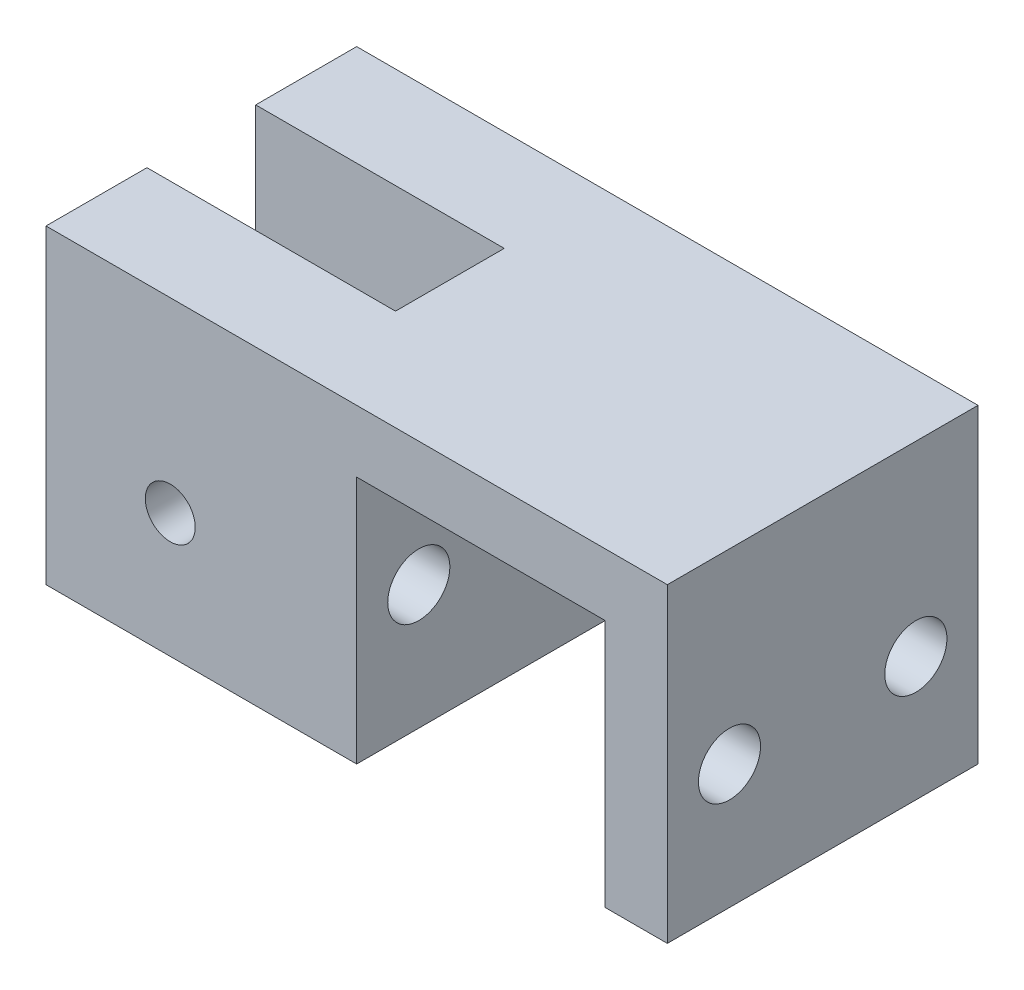
SolidWorks part; units mm, degrees
material "Delrin 2700 NC010, Low Viscosity Acetal Copolymer (SS)"
ref_plane "Front" through (0, 0, 0) normal (0, 0, 1) x (1, 0, 0)
ref_plane "Top" through (0, 0, 0) normal (0, 1, 0) x (1, 0, 0)
ref_plane "Right" through (0, 0, 0) normal (1, 0, 0) x (0, 0, -1)
sketch "Sketch1" plane through (0, 0, 0) normal (0, 0, 1) x (1, 0, 0)
  line L0 (0, 0) -> (0, 25.4)
  line L1 (0, 25.4) -> (25.4, 25.4)
  line L2 (25.4, 25.4) -> (25.4, 0)
  line L3 (25.4, 0) -> (31.75, 0)
  line L4 (31.75, 0) -> (31.75, 31.75)
  line L5 (31.75, 31.75) -> (-31.75, 31.75)
  line L6 (-31.75, 31.75) -> (-31.75, 0)
  line L7 (-31.75, 0) -> (0, 0)
  dimension "D1" = 6.35
  dimension "D2" = 25.4
  dimension "D3" = 6.35
  dimension "D4" = 31.75
extrude "Boss-Extrude1" add sketch "Sketch1" along normal mid plane 31.75
sketch "Sketch2" plane through (0, 31.75, 0) normal (0, 1, 0) x (1, 0, 0)
  line L0 (-31.75, -15.875) -> (-31.75, 15.875) construction
  line L1 (-31.75, 5.5562) -> (-6.35, 5.5562)
  line L2 (-31.75, 5.5562) -> (-31.75, -5.5563)
  line L3 (-31.75, -5.5563) -> (-6.35, -5.5563)
  line L4 (-6.35, 5.5562) -> (-6.35, -5.5563)
  line L5 (-31.75, 15.875) -> (-6.35, 5.5562) construction
  line L6 (-6.35, -5.5563) -> (-31.75, -15.875) construction
  dimension "D1" = 11.1125
  dimension "D2" = 25.4
extrude "Cut-Extrude1" cut sketch "Sketch2" against normal through all
sketch "Sketch5" plane through (31.75, 0, 0) normal (1, 0, 0) x (0, 0, -1)
  line L0 (-15.875, 0) -> (-9.525, 12.7) construction
  line L5 (9.525, 12.7) -> (15.875, 0) construction
  line L7 (-15.875, 0) -> (15.875, 0) construction
  point P0 (-9.525, 12.7)
  point P2 (9.525, 12.7)
  dimension "D1" = 19.05
  dimension "D2" = 12.7
hole_wizard "1/4 (0.25) Diameter Hole1" positions "Sketch5" profile "Sketch4" hole size "1/4" standard "ANSI Inch"
sketch "Sketch4" plane through (31.75, 12.7, 9.525) normal (0, 1, 0) x (0, 0, -1)
  line L0 (0, 0) -> (0, 46.3577)
  line L1 (0, 46.3577) -> (3.175, 44.45)
  line L2 (3.175, 44.45) -> (3.175, 0)
  line L5 (3.175, 0) -> (0, 0)
  line L10 (0, 46.3577) -> (-3.175, 44.45) construction
  line L11 (0, -6.35) -> (0, 107.95) construction
  dimension "Hole Dia." = 6.35
  dimension "Hole Depth" = 44.45
  dimension "Drill Angle" = 118
sketch "Sketch8" plane through (0, 0, 15.875) normal (0, 0, 1) x (1, 0, 0)
  line L0 (-6.35, 0) -> (-6.35, 31.75) construction
  line L1 (-31.75, 0) -> (0, 0) construction
  circle A0 centre (-19.05, 12.7) radius 11.1125 construction
  point P0 (-19.05, 12.7)
  dimension "D1" = 22.225
  dimension "D2" = 12.7
  dimension "D3" = 12.7
hole_wizard "#10 Clearance Hole1" positions "Sketch8" profile "Sketch7" hole size "#10" standard "ANSI Inch" end condition through all
sketch "Sketch7" plane through (-19.05, 12.7, 15.875) normal (1, 0, 0) x (0, -1, 0)
  line L0 (0, 0) -> (0, 31.75)
  line L1 (0, 31.75) -> (2.5527, 31.75)
  line L2 (2.5527, 31.75) -> (2.5527, 0)
  line L5 (2.5527, 0) -> (0, 0)
  line L11 (0, -6.35) -> (0, 107.95) construction
  dimension "Thru Hole Dia." = 5.1054
  dimension "Thru Hole Depth" = 31.75
